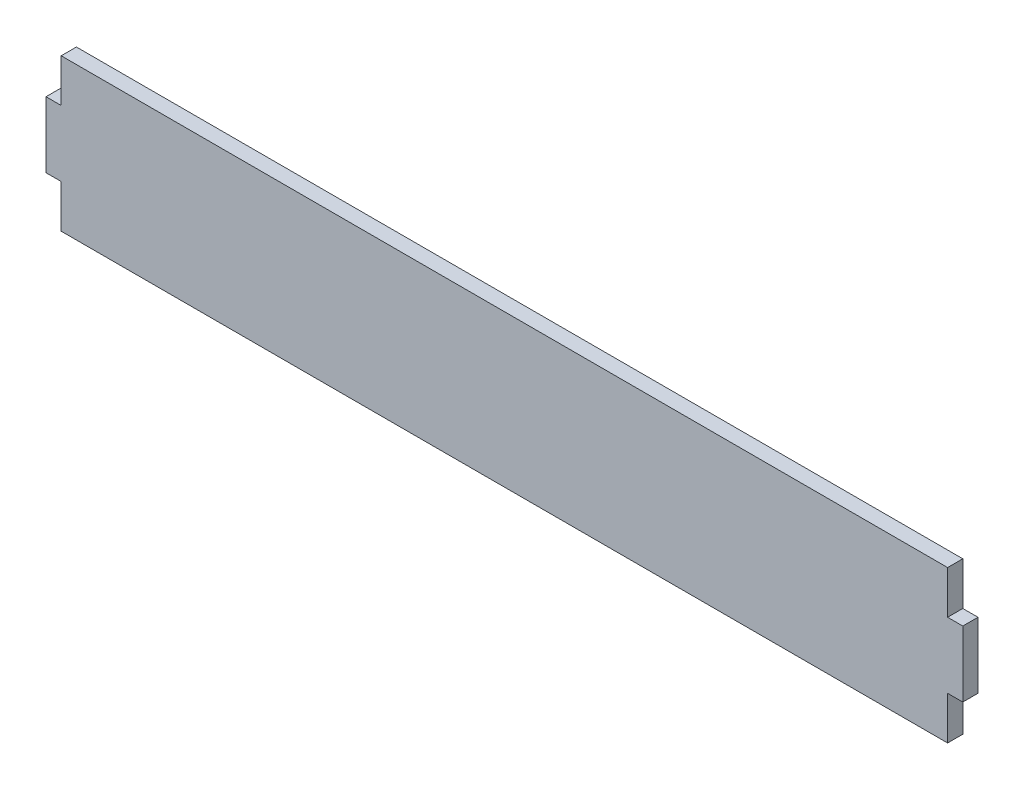
SolidWorks part; units mm, degrees
ref_plane "Front Plane" through (0, 0, 0) normal (0, 0, 1) x (1, 0, 0)
ref_plane "Top Plane" through (0, 0, 0) normal (0, 1, 0) x (1, 0, 0)
ref_plane "Right Plane" through (0, 0, 0) normal (1, 0, 0) x (0, 0, -1)
sketch "Sketch1" plane through (0, 0, 0) normal (0, 0, 1) x (1, 0, 0)
  line L0 (3, 21.5) -> (3, 30)
  line L1 (3, 0) -> (178, 0)
  line L3 (3, 30) -> (178, 30)
  line L5 (0, 21.5) -> (3, 21.5)
  line L6 (0, 21.5) -> (0, 8.5)
  line L7 (0, 8.5) -> (3, 8.5)
  line L10 (0, 0) -> (3, 0) construction
  line L11 (3, 8.5) -> (3, 0)
  line L12 (0, 8.5) -> (0, 0) construction
  line L13 (90.5, 15) -> (90.5, 3.5137) construction
  line L14 (0, 15) -> (181, 15) construction
  line L15 (181, -91.081) -> (181, 87.3117) construction
  line L16 (178, 8.5) -> (178, 0)
  line L17 (181, 8.5) -> (178, 8.5)
  line L18 (178, 21.5) -> (178, 30)
  line L19 (181, 21.5) -> (178, 21.5)
  line L20 (181, 21.5) -> (181, 8.5)
  dimension "D1" = 30
  dimension "D2" = 13
  dimension "D3" = 3
extrude "Boss-Extrude1" add sketch "Sketch1" along normal blind 3
